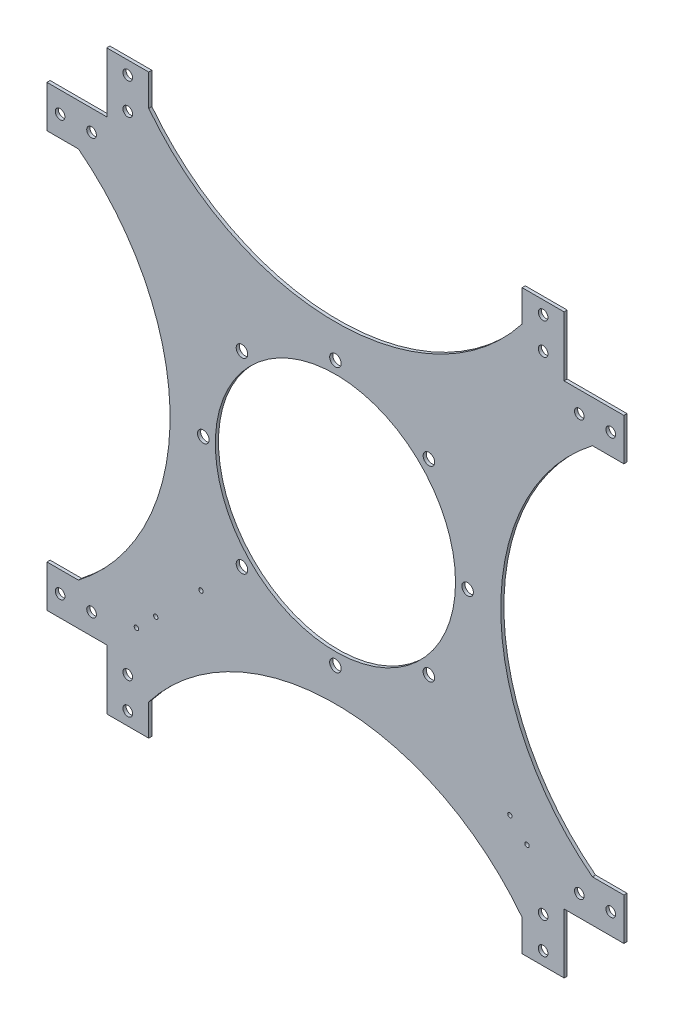
SolidWorks part; units mm, degrees
ref_plane "Front Plane" through (0, 0, 0) normal (0, 0, 1) x (1, 0, 0)
ref_plane "Top Plane" through (0, 0, 0) normal (0, 1, 0) x (1, 0, 0)
ref_plane "Right Plane" through (0, 0, 0) normal (1, 0, 0) x (0, 0, -1)
sketch "Sketch1" plane through (0, 0, 0) normal (0, 0, 1) x (1, 0, 0)
  line L0 (0, 0) -> (367.2182, 0) construction
  line L1 (0, 0) -> (0, -316.5866) construction
  line L2 (0, 0) -> (218, 218) construction
  line L3 (0, 0) -> (218, -218) construction
  line L4 (218, 218) -> (218, 275)
  line L5 (218, 218) -> (275, 218)
  line L6 (218, 275) -> (178, 275)
  line L7 (178, 275) -> (178, 245)
  line L8 (0, 0) -> (-218, 218) construction
  line L9 (0, 0) -> (-218, -218) construction
  line L10 (0, 0) -> (-199.7109, 0) construction
  line L11 (-218, 218) -> (-218, 275)
  line L12 (-218, 275) -> (-178, 275)
  line L13 (-178, 275) -> (-178, 245)
  line L14 (218, -218) -> (275, -218)
  line L15 (275, -218) -> (275, -178)
  line L16 (275, -178) -> (245, -178)
  line L17 (275, 218) -> (275, 178)
  line L18 (275, 178) -> (245, 178)
  line L19 (218, -218) -> (218, -275)
  line L20 (218, -275) -> (178, -275)
  line L21 (178, -275) -> (178, -245)
  line L22 (-178, -275) -> (-178, -245)
  line L23 (-218, -275) -> (-178, -275)
  line L24 (-218, -218) -> (-218, -275)
  line L25 (-218, -218) -> (-275, -218)
  line L26 (-275, -218) -> (-275, -178)
  line L27 (-275, -178) -> (-245, -178)
  line L28 (-275, 178) -> (-245, 178)
  line L29 (-275, 218) -> (-275, 178)
  line L30 (-218, 218) -> (-275, 218)
  circle A0 centre (0, 0) radius 114.5
  arc A1 (-178, 245) -> (178, 245) centre (0, 382.6263) ccw
  arc A2 (245, 178) -> (245, -178) centre (382.6263, 0) ccw
  arc A3 (-178, -245) -> (178, -245) centre (0, -382.6263) cw
  arc A4 (-245, 178) -> (-245, -178) centre (-382.6263, 0) cw
  dimension "D4" = 229
  dimension "D9" = 225
  dimension "D1" = 45
  dimension "D3" = 57
  dimension "D5" = 40
  dimension "D6" = 45
  dimension "D7" = 45
  dimension "D8" = 30
  dimension "D10" = 275
sheet metal parameters "Sheet-Metal1" thickness 3 parameters "D1"=1
base flange "Base-Flange1" sketch "Sketch1" thickness 3 reverse thickness direction yes parameters "D1"=1
sketch "Sketch2" plane through (0, 0, 3) normal (0, 0, 1) x (1, 0, 0)
  line L0 (218, 218) -> (218, 275) construction
  line L1 (218, 275) -> (178, 275) construction
  line L2 (275, 178) -> (275, 218) construction
  line L3 (275, 218) -> (218, 218) construction
  line L4 (0, 0) -> (260.8486, 0) construction
  line L5 (0, 0) -> (0, -250.4708) construction
  circle A0 centre (198, 262.5) radius 4.6
  circle A1 centre (198, 232.5) radius 4.6
  circle A2 centre (232.5, 198) radius 4.6
  circle A3 centre (262.5, 198) radius 4.6
  circle A4 centre (262.5, -198) radius 4.6
  circle A5 centre (232.5, -198) radius 4.6
  circle A6 centre (198, -232.5) radius 4.6
  circle A7 centre (198, -262.5) radius 4.6
  circle A8 centre (-198, -262.5) radius 4.6
  circle A9 centre (-198, -232.5) radius 4.6
  circle A10 centre (-232.5, -198) radius 4.6
  circle A11 centre (-262.5, -198) radius 4.6
  circle A12 centre (-262.5, 198) radius 4.6
  circle A13 centre (-232.5, 198) radius 4.6
  circle A14 centre (-198, 232.5) radius 4.6
  circle A15 centre (-198, 262.5) radius 4.6
  point P8 (218, 246.5)
  dimension "D2" = 9.2
  dimension "D1" = 20
  dimension "D3" = 12.5
  dimension "D4" = 30
  dimension "D5" = 30
  dimension "D6" = 12.5
  dimension "D7" = 20
extrude "Extrude1" cut sketch "Sketch2" against normal blind 3 normal cut yes
sketch "Sketch3" plane through (0, 0, 3) normal (0, 0, 1) x (1, 0, 0)
  line L0 (0, 0) -> (220.4396, 0) construction
  line L1 (0, 0) -> (0, -219.5819) construction
  line L2 (0, 0) -> (178.1909, 178.1909) construction
  circle A0 centre (0, 0) radius 126 construction
  circle A1 centre (0, 126) radius 5.5
  circle A2 centre (-126, 0) radius 5.5 construction
  circle A3 centre (0, -126) radius 5.5 construction
  circle A4 centre (126, 0) radius 5.5 construction
  dimension "D2" = 11
  dimension "D3" = 252
  dimension "D1" = 45
extrude "Extrude2" cut sketch "Sketch3" against normal blind 3 normal cut yes
pattern_circular "CirPattern1" count 8 over 360 about axis through (0, 0, 3) along (0, 0, 1) of "Extrude2"
sketch "Sketch4" plane through (0, 0, 3) normal (0, 0, 1) x (1, 0, 0)
  line L0 (-218, -218) -> (0, 0) construction
  line L1 (0, 0) -> (218, -218) construction
  circle A0 centre (-189.7157, -189.7157) radius 2.1
  circle A1 centre (-171.331, -171.331) radius 2.1
  circle A2 centre (-128.1974, -128.1974) radius 2.1
  circle A3 centre (166.3812, -166.3812) radius 2.1
  circle A4 centre (182.6447, -182.6447) radius 2.1
  dimension "D4" = 4.2
  dimension "D1" = 87
  dimension "D2" = 26
  dimension "D3" = 40
  dimension "D5" = 23
  dimension "D6" = 50
extrude "Cut-Extrude1" cut sketch "Sketch4" against normal blind 3 normal cut yes
flat pattern "Flat-Pattern1" [suppressed]
sketch "Bend-Lines1" plane through (0, 0, 0) normal (0, 1, 0) x (-1, 0, 0)
